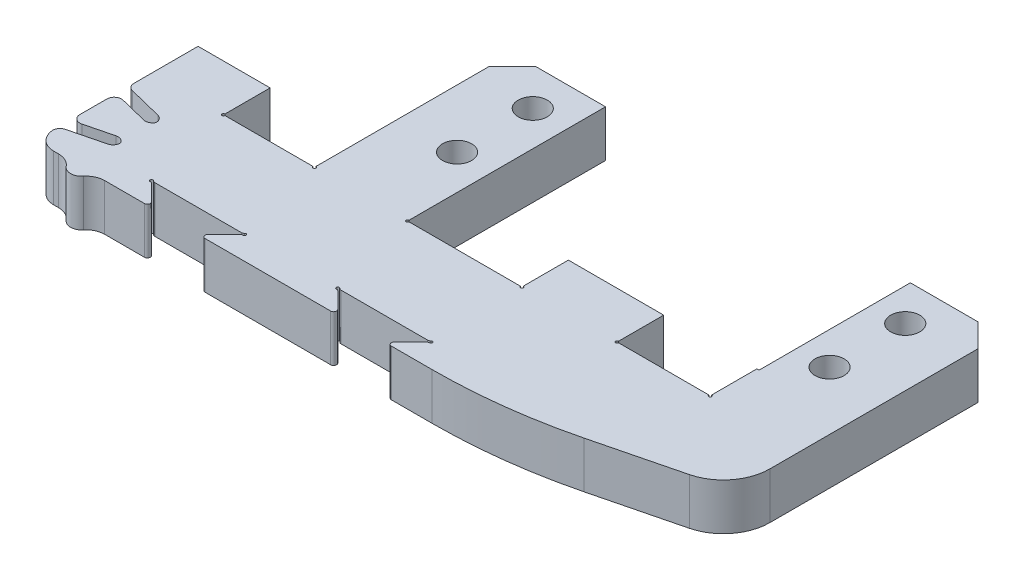
SolidWorks part; units mm, degrees
ref_plane "Front Plane" through (0, 0, 0) normal (0, 0, 1) x (1, 0, 0)
ref_plane "Top Plane" through (0, 0, 0) normal (0, 1, 0) x (1, 0, 0)
ref_plane "Right Plane" through (0, 0, 0) normal (1, 0, 0) x (0, 0, -1)
sketch "Sketch2" plane through (0, 0, 0) normal (0, 0, 1) x (1, 0, 0)
  line L0 (-33.925, 56.4924) -> (-33.925, 29.3688) construction
  line L1 (51.8, -23.0187) -> (-33.925, -23.0187)
  line L3 (48.625, -29.3687) -> (-33.925, -29.3687)
  line L4 (-33.925, -23.0187) -> (-33.925, -29.3687)
  line L6 (48.625, -29.3687) -> (54.975, -29.3687)
  line L8 (51.8, -23.0187) -> (54.975, -23.0187)
  line L9 (54.975, -29.3687) -> (54.975, -23.0187)
  dimension "D1" = 3.175
extrude "Boss-Extrude1" add sketch "Sketch2" along normal blind 15.875
sketch "Sketch3" plane through (0, 0, 0) normal (0, 0, -1) x (-1, 0, 0)
  line L0 (-54.975, -23.0187) -> (33.925, -23.0187) construction
  line L1 (11.7, -23.0187) -> (-1, -23.0187)
  line L2 (11.7, -23.0187) -> (11.7, -29.3687)
  line L3 (11.7, -29.3687) -> (-1, -29.3687)
  line L4 (-1, -23.0187) -> (-1, -29.3687)
  line L5 (11.7, -23.0187) -> (11.7, -29.3687) construction
  line L6 (33.925, -29.3687) -> (-54.975, -29.3687) construction
  line L7 (-1, -1.3969) -> (-1, -29.3687) construction
  line L10 (-54.975, -23.0187) -> (33.925, -23.0187) construction
  line L11 (-54.975, -29.3687) -> (-42.275, -29.3687)
  line L12 (-54.975, -29.3687) -> (-54.975, -23.0187)
  line L13 (-54.975, -23.0187) -> (-42.275, -23.0187)
  line L14 (-42.275, -29.3687) -> (-42.275, -23.0187)
  dimension "D1" = 12.7
extrude "Boss-Extrude2" add sketch "Sketch3" along normal up to surface (26.9875 mm away)
sketch "Sketch5" plane through (0, -23.0187, 0) normal (0, 1, 0) x (1, 0, 0)
  line L0 (54.975, -15.875) -> (-33.925, -15.875) construction
  line L2 (-33.925, -15.875) -> (-33.925, 0) construction
  circle A0 centre (-27.575, -15.875) radius 1.5
  dimension "D1" = 3
  dimension "D2" = 6.35
extrude "Boss-Extrude4" add sketch "Sketch5" against normal blind 6.35
fillet "Fillet1" radius 2.54 1 edges at (-26.075, -26.1937, 15.875)
sketch "Sketch6" plane through (0, -23.0187, 0) normal (0, 1, 0) x (1, 0, 0)
  line L0 (-33.925, -7.9375) -> (48.625, -7.9375) construction
  line L1 (-33.925, -15.875) -> (-33.925, 0) construction
  line L2 (-33.925, -12.7) -> (-33.925, -3.175) construction
  line L3 (-27.575, -11.1125) -> (-27.575, -4.7625) construction
  line L4 (-33.925, -3.175) -> (-27.575, -4.7625)
  line L5 (-34.31, -4.7151) -> (-27.96, -6.3026)
  line L6 (-33.925, -12.7) -> (-27.575, -11.1125)
  line L7 (-34.31, -11.1599) -> (-27.96, -9.5724)
  line L8 (-27.96, -6.3026) -> (-27.575, -4.7625)
  line L9 (-34.31, -4.7151) -> (-33.925, -3.175)
  line L10 (-33.925, -12.7) -> (-34.31, -11.1599)
  line L11 (-27.575, -11.1125) -> (-27.96, -9.5724)
  point P7 (-33.925, -7.9375)
  point P10 (-27.575, -7.9375)
  dimension "D1" = 9.525
  dimension "D2" = 6.35
  dimension "D3" = 6.35
  dimension "D4" = 1.5875
extrude "Cut-Extrude1" cut sketch "Sketch6" against normal through all
fillet "Fillet3" radius 1 8 edges at (-27.575, -26.1938, 11.1125) (-27.96, -26.1938, 9.5724) (-27.96, -26.1938, 6.3026) (-27.575, -26.1938, 4.7625) (-33.925, -26.1938, 3.175) (-33.925, -26.1938, 4.8114) (-33.925, -26.1938, 11.0636) (-33.925, -26.1938, 12.7)
sketch "Sketch7" plane through (0, -29.3688, 0) normal (0, -1, 0) x (-1, 0, 0)
  line L0 (-54.975, -15.875) -> (-54.975, -9.525)
  line L1 (-54.975, -15.875) -> (-54.975, 26.9875) construction
  line L2 (-54.975, -9.525) -> (-29.575, -15.875)
  line L3 (24.4333, -15.875) -> (-54.975, -15.875) construction
  line L4 (-29.575, -15.875) -> (-54.975, -15.875)
  dimension "D1" = 6.35
  dimension "D2" = 25.4
extrude "Cut-Extrude2" cut sketch "Sketch7" against normal blind 6.35
fillet "Fillet4" radius 6.35 1 edges at (54.975, -26.1937, 9.525)
fillet "Fillet5" radius 76.2 1 edges at (29.575, -26.1937, 15.875)
sketch "Sketch8" plane through (0, 0, 0) normal (0, 0, -1) x (-1, 0, 0)
  line L0 (11.7, -23.0187) -> (33.925, -23.0187) construction
  line L1 (33.925, -29.3687) -> (24.1, -29.3687)
  line L2 (33.925, -29.3687) -> (33.925, -23.0187)
  line L3 (33.925, -23.0187) -> (24.1, -23.0187)
  line L4 (24.1, -29.3687) -> (24.1, -23.0187)
  dimension "D1" = 9.825
extrude "Boss-Extrude5" add sketch "Sketch8" along normal blind 6.35
sketch "Sketch9" plane through (0, -23.0187, 0) normal (0, 1, 0) x (1, 0, 0)
  line L0 (42.275, 0) -> (1, 0) construction
  line L1 (42.275, 26.9875) -> (42.575, 26.9875)
  line L2 (42.275, 26.9875) -> (42.275, 6.35)
  line L3 (42.275, 6.35) -> (42.575, 6.35)
  line L4 (42.575, 26.9875) -> (42.575, 6.35)
  dimension "D1" = 0.3
  dimension "D2" = 6.35
extrude "Cut-Extrude3" cut sketch "Sketch9" against normal through all
fillet "Fillet6" radius 2.54 1 edges at (-29.075, -26.1937, 15.875)
fillet "Fillet7" radius 2.54 1 edges at (-33.925, -26.1937, 15.875)
sketch "Sketch10" plane through (0, -29.3688, 0) normal (0, -1, 0) x (-1, 0, 0)
  circle A0 centre (-47.0375, 21.8281) radius 1.9844
  circle A1 centre (-47.0375, 11.5094) radius 1.9844
  circle A2 centre (3.7625, 11.5094) radius 1.9844
  circle A3 centre (3.7625, 21.8281) radius 1.9844
extrude "Cut-Extrude4" cut sketch "Sketch10" against normal through all
chamfer "Chamfer1" distance 3.175 angle 45 2 edges at (54.975, -26.1937, -26.9875) (-11.7, -26.1937, -26.9875)
sketch "Sketch11" plane through (0, 0, 0) normal (0, 0, -1) x (-1, 0, 0)
  line L0 (-1, -29.3687) -> (-42.275, -29.3687) construction
  line L1 (-29.575, -29.3687) -> (-16.575, -29.3687)
  line L2 (-29.575, -29.3687) -> (-29.575, -23.0187)
  line L3 (-29.575, -23.0187) -> (-16.575, -23.0187)
  line L4 (-16.575, -29.3687) -> (-16.575, -23.0187)
  line L5 (-42.275, -23.0187) -> (-1, -23.0187) construction
  dimension "D1" = 13
  dimension "D2" = 25.4
extrude "Boss-Extrude6" add sketch "Sketch11" along normal blind 6.35
sketch "Sketch12" plane through (0, -23.0187, 0) normal (0, 1, 0) x (1, 0, 0)
  circle A0 centre (-24.1, 0) radius 0.1984
  circle A1 centre (-11.7, 0) radius 0.1984
  circle A2 centre (1, 0) radius 0.1984
  circle A3 centre (16.575, 0) radius 0.1984
  circle A4 centre (29.575, 0) radius 0.1984
  circle A5 centre (42.275, 0) radius 0.1984
  dimension "D1" = 0.3969
  dimension "D2" = 0.3969
  dimension "D3" = 0.3969
  dimension "D4" = 0.3969
  dimension "D5" = 0.3969
  dimension "D6" = 0.3969
extrude "Cut-Extrude5" cut sketch "Sketch12" against normal through all
sketch "Sketch13" plane through (0, -23.0187, 0) normal (0, 1, 0) x (1, 0, 0)
  line L0 (-11.8984, 0) -> (-23.9016, 0) construction
  line L1 (-21.225, -12.7) -> (-8.525, -12.7)
  line L2 (16.875, -12.7) -> (13.7, -15.875)
  line L3 (-18.05, -15.875) -> (-11.7, -15.875)
  line L4 (4.175, -12.7) -> (16.875, -12.7)
  line L6 (-21.225, -12.7) -> (-18.05, -15.875)
  line L7 (-8.525, -12.7) -> (-11.7, -15.875)
  line L8 (4.175, -12.7) -> (7.35, -15.875)
  line L9 (7.35, -15.875) -> (13.7, -15.875)
  dimension "D1" = 12.7
  dimension "D2" = 2
  dimension "D3" = 12.7
extrude "Cut-Extrude6" cut sketch "Sketch13" against normal blind 6.35
fillet "Fillet8" radius 0.3969 4 edges at (-18.05, -26.1937, 15.875) (7.35, -26.1937, 15.875) (13.7, -26.1937, 15.875) (-11.7, -26.1937, 15.875)
sketch "Sketch14" plane through (0, -23.0187, 0) normal (0, 1, 0) x (1, 0, 0)
  circle A0 centre (-21.225, -12.7) radius 0.1984
  circle A1 centre (-8.525, -12.7) radius 0.1984
  circle A2 centre (4.175, -12.7) radius 0.1984
  circle A3 centre (16.875, -12.7) radius 0.1984
  dimension "D1" = 0.3969
  dimension "D2" = 0.3969
  dimension "D3" = 0.3969
  dimension "D4" = 0.3969
extrude "Cut-Extrude7" cut sketch "Sketch14" against normal through all
fillet "Fillet9" radius 0.3969 8 edges at (4.3153, -26.1938, 12.8403) (16.7347, -26.1937, 12.8403) (16.6766, -26.1938, 12.7) (4.3734, -26.1937, 12.7) (-8.7234, -26.1938, 12.7) (-8.6653, -26.1937, 12.8403) (-21.0847, -26.1938, 12.8403) (-21.0266, -26.1937, 12.7)
